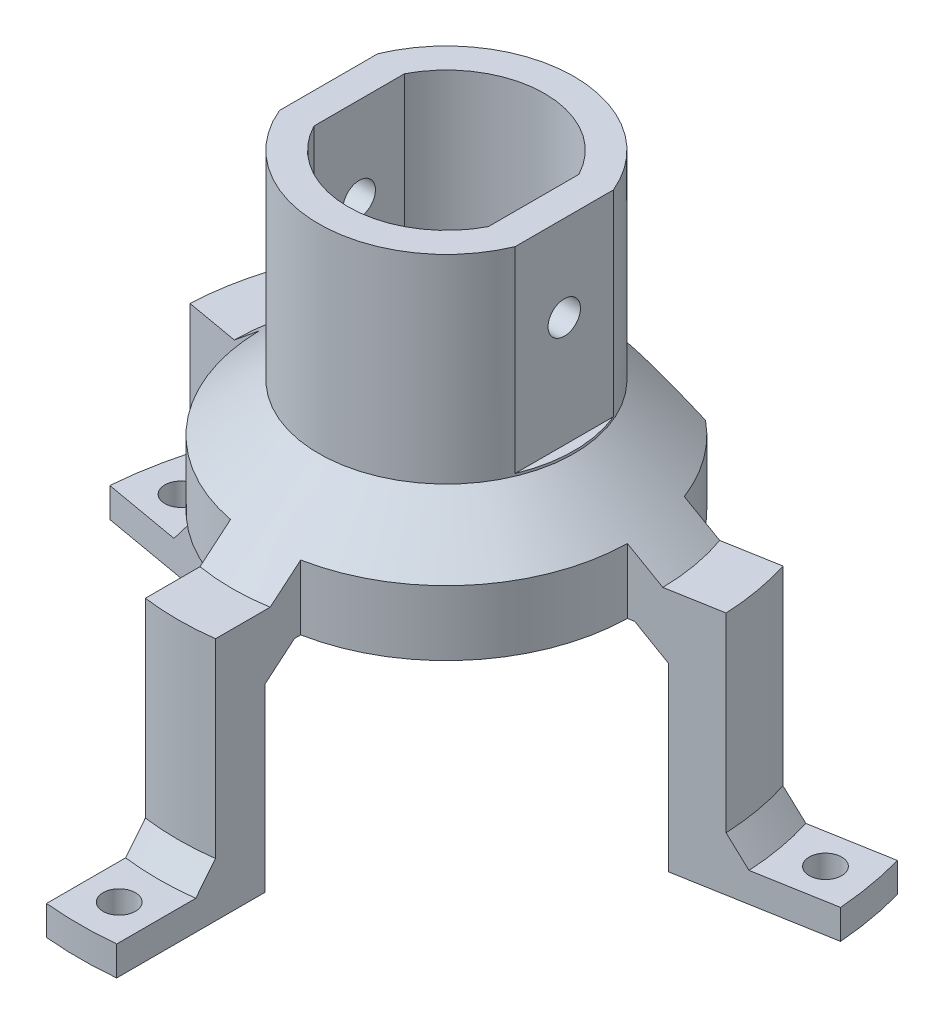
SolidWorks part; units mm, degrees
ref_plane "Front Plane" through (0, 0, 0) normal (0, 0, 1) x (1, 0, 0)
ref_plane "Top Plane" through (0, 0, 0) normal (0, 1, 0) x (1, 0, 0)
ref_plane "Right Plane" through (0, 0, 0) normal (1, 0, 0) x (0, 0, -1)
sketch "Sketch2" plane through (0, 0, 0) normal (0, 0, 1) x (1, 0, 0)
  line L0 (-4.74, 0) -> (4.74, 0) construction
  line L1 (-4.74, 0) -> (-4.74, 8) construction
  line L2 (-4.74, 8) -> (-1, 8) construction
  line L3 (-1, 8) -> (-1, 10.53) construction
  line L4 (-1, 10.53) -> (-7, 10.53) construction
  line L5 (-7, 10.53) -> (-7, 14.08) construction
  line L6 (-7, 14.08) -> (-9.75, 14.08) construction
  line L7 (-9.75, 14.08) -> (-9.75, 91.98) construction
  line L8 (-9.75, 91.98) -> (9.75, 91.98) construction
  line L9 (9.75, 91.98) -> (9.75, 14.08) construction
  line L10 (9.75, 14.08) -> (7, 14.08) construction
  line L11 (4.74, 0) -> (4.74, 8) construction
  line L12 (4.74, 8) -> (1, 8) construction
  line L13 (1, 8) -> (1, 10.53) construction
  line L14 (1, 10.53) -> (7, 10.53) construction
  line L15 (7, 10.53) -> (7, 14.08) construction
  point P19 (9.75, 53.03)
  dimension "D1" = 9.48
  dimension "D2" = 1
  dimension "D3" = 8
  dimension "D4" = 2
  dimension "D5" = 14
  dimension "D6" = 7
  dimension "D7" = 19.5
  dimension "D8" = 9.75
  dimension "D9" = 3.55
  dimension "D10" = 2.53
  dimension "D11" = 42.5
sketch "Sketch3" plane through (0, 0, 0) normal (0, 0, 1) x (1, 0, 0)
  line L0 (7, 10.58) -> (7, 14.08)
  line L3 (-25.4, -27.9481) -> (25.4, -27.9481) construction
  line L4 (0, -36.7735) -> (0, 62.135) construction
  line L5 (44.625, -31.1795) -> (74.625, -31.1795)
  line L6 (7, 14.08) -> (20, 14.08)
  line L7 (20, 14.08) -> (20, 74.08)
  line L8 (14.4437, 62.135) -> (20, 62.135) construction
  line L9 (74.625, -31.1795) -> (74.625, -25.1795)
  line L10 (11, 14.08) -> (11, 45.02) construction
  line L11 (20, 74.08) -> (26, 74.08)
  line L12 (26, 74.08) -> (26, 33.58)
  line L14 (54.625, 18.58) -> (54.625, -20.1795)
  line L16 (7, 10.58) -> (38.75, 10.58)
  line L17 (38.75, 10.58) -> (44.625, 5.58)
  line L18 (44.625, 5.58) -> (44.625, -31.1795)
  line L19 (26, 33.58) -> (43.625, 18.58)
  line L20 (43.625, 18.58) -> (54.625, 18.58)
  line L21 (14.4437, 62.135) -> (14.4438, 51.025) construction
  line L22 (14.4438, 51.025) -> (20, 51.025) construction
  line L23 (20, 51.025) -> (20, 62.135) construction
  line L24 (74.625, -25.1795) -> (58.625, -25.1795)
  line L25 (58.625, -25.1795) -> (54.625, -20.1795)
  line L26 (61.0687, -25.1795) -> (61.0687, -19.6195) construction
  line L27 (61.0687, -19.6195) -> (72.1812, -19.6195) construction
  line L28 (72.1812, -19.6195) -> (72.1812, -25.1795) construction
  point P8 (0, -27.9481)
  point P31 (66.625, -19.6195)
  point P32 (66.625, -25.1795)
  point P36 (14.4437, 56.58)
  dimension "D1" = 50.8
  dimension "D2" = 5.5562
  dimension "D3" = 20
  dimension "D4" = 11
  dimension "D5" = 60
  dimension "D6" = 6
  dimension "D7" = 47.625
  dimension "D8" = 10
  dimension "D9" = 31.75
  dimension "D10" = 3.5
  dimension "D11" = 5
  dimension "D12" = 8
  dimension "D13" = 15
  dimension "D14" = 5
  dimension "D15" = 6
  dimension "D16" = 30
  dimension "D17" = 11.1125
  dimension "D18" = 49.7595
  dimension "D19" = 16
  dimension "D20" = 5.56
  dimension "D21" = 11.11
  dimension "D22" = 42.5
revolve "Revolve1" add sketch "Sketch3" angle 360 about L4
sketch "Sketch4" plane through (0, 74.08, 0) normal (0, 1, 0) x (1, 0, 0)
  line L0 (-7.1438, -74.2823) -> (-7.1438, -36.8133)
  line L1 (0, 0) -> (-73.4913, 12.9585) construction
  line L2 (7.1437, -74.2823) -> (7.1437, -36.8133)
  line L3 (0, 0) -> (0, 79.5976) construction
  line L4 (-71.9133, 19.9342) -> (-35.0135, 13.4278)
  line L5 (-74.3943, 5.8638) -> (-37.4945, -0.6427)
  line L6 (74.3943, 5.8638) -> (37.4945, -0.6427)
  line L7 (71.9133, 19.9342) -> (35.0135, 13.4278)
  line L8 (0, 0) -> (-35.0135, 13.4278) construction
  line L9 (0, 0) -> (-7.1438, -36.8133) construction
  line L10 (-73.4913, 12.9585) -> (-57.7344, 10.1801) construction
  line L11 (-65.6128, 11.5693) -> (-66.063, 9.016) construction
  line L12 (0, 0) -> (-65.6128, 11.5693) construction
  line L13 (0, 0) -> (0, -66.625) construction
  arc A0 (-7.1438, -74.2823) -> (7.1437, -74.2823) centre (0, 0) ccw
  circle A3 centre (0, 0) radius 74.625 construction
  arc A4 (-71.9133, 19.9342) -> (-74.3943, 5.8638) centre (0, 0) ccw
  arc A5 (-37.4945, -0.6427) -> (-7.1438, -36.8133) centre (0, 0) ccw
  arc A6 (74.3943, 5.8638) -> (71.9133, 19.9342) centre (0, 0) ccw
  arc A7 (7.1437, -36.8133) -> (37.4945, -0.6427) centre (0, 0) ccw
  arc A8 (35.0135, 13.4278) -> (-35.0135, 13.4278) centre (0, 0) ccw
  circle A9 centre (0, 0) radius 74.625
  circle A10 centre (0, 0) radius 58.625 construction
  circle A11 centre (-65.6128, 11.5693) radius 3.3
  circle A12 centre (0, -66.625) radius 3.3
  circle A13 centre (65.6128, 11.5693) radius 3.3
  point P8 (-53.4634, 16.681)
  dimension "D7" = 3
  dimension "D1" = 75
  dimension "D5" = 6.6
  dimension "D2" = 80
  dimension "D3" = 7.1437
  dimension "D4" = 100
  dimension "D6" = 100
  dimension "D8" = 66.625
extrude "Cut-Extrude1" cut sketch "Sketch4" against normal through all contours L7 A9 L4 A8 | L5 A9 L0 A5 | L2 A9 L6 A7 | A11 | A12 | A13 region at (-40.6997, 74.08, 34.1511) region at (40.6997, 74.08, 34.1511) region at (0, 74.08, -43.7839)
fillet "Fillet1" [suppressed] radius 1
fillet "Fillet2" [suppressed] radius 1
fillet "Fillet3" [suppressed] radius 1
sketch "Sketch5" plane through (0, 74.08, 0) normal (0, 1, 0) x (1, 0, 0)
  line L0 (-17.75, -9.2162) -> (-17.75, 9.2162)
  line L1 (0, 17.2156) -> (0, -17.9636) construction
  line L2 (17.75, -9.2162) -> (17.75, 9.2162)
  circle A1 centre (0, 0) radius 20 construction
  arc A2 (-17.75, 9.2162) -> (-17.75, -9.2162) centre (0, 0) ccw
  arc A3 (17.75, 9.2162) -> (17.75, -9.2162) centre (0, 0) cw
  dimension "D1" = 17.75
extrude "Boss-Extrude1" add sketch "Sketch5" against normal up to next
sketch "Sketch6" plane through (0, 74.08, 0) normal (0, 1, 0) x (1, 0, 0)
  line L0 (-24, 10) -> (-24, -10)
  line L1 (0, 17.4487) -> (0, -16.9274) construction
  line L2 (24, 10) -> (24, -10)
  circle A0 centre (0, 0) radius 26 construction
  arc A1 (-24, 10) -> (-24, -10) centre (0, 0) ccw
  arc A2 (24, 10) -> (24, -10) centre (0, 0) cw
  dimension "D1" = 24
extrude "Cut-Extrude2" cut sketch "Sketch6" against normal blind 40
sketch "Sketch7" plane through (24, 0, 0) normal (1, 0, 0) x (0, 0, -1)
  line L0 (7, 14.08) -> (-7, 14.08) construction
  line L1 (10, 34.08) -> (10, 74.08) construction
  circle A0 centre (0, 56.58) radius 3.3
  dimension "D1" = 6.6
  dimension "D2" = 42.5
  dimension "D3" = 10
extrude "Cut-Extrude3" cut sketch "Sketch7" against normal through all
sketch "Sketch8" plane through (0, 0, 0) normal (0, 1, 0) x (1, 0, 0)
  line L0 (73.2179, 47.1339) -> (-64.466, 47.1339)
  arc A0 (-64.466, 47.1339) -> (73.2179, 47.1339) centre (4.376, 158.6897) ccw
  arc A1 (-37.398, 36.5175) -> (-36.0634, 36.0692) centre (4.376, 158.6897) ccw construction
  point P7 (4.376, 47.1339)
  dimension "D1" = 1.9707
  dimension "D2" = 137.6839
extrude "Cut-Extrude4" cut sketch "Sketch8" against normal through all both and the other way through all
